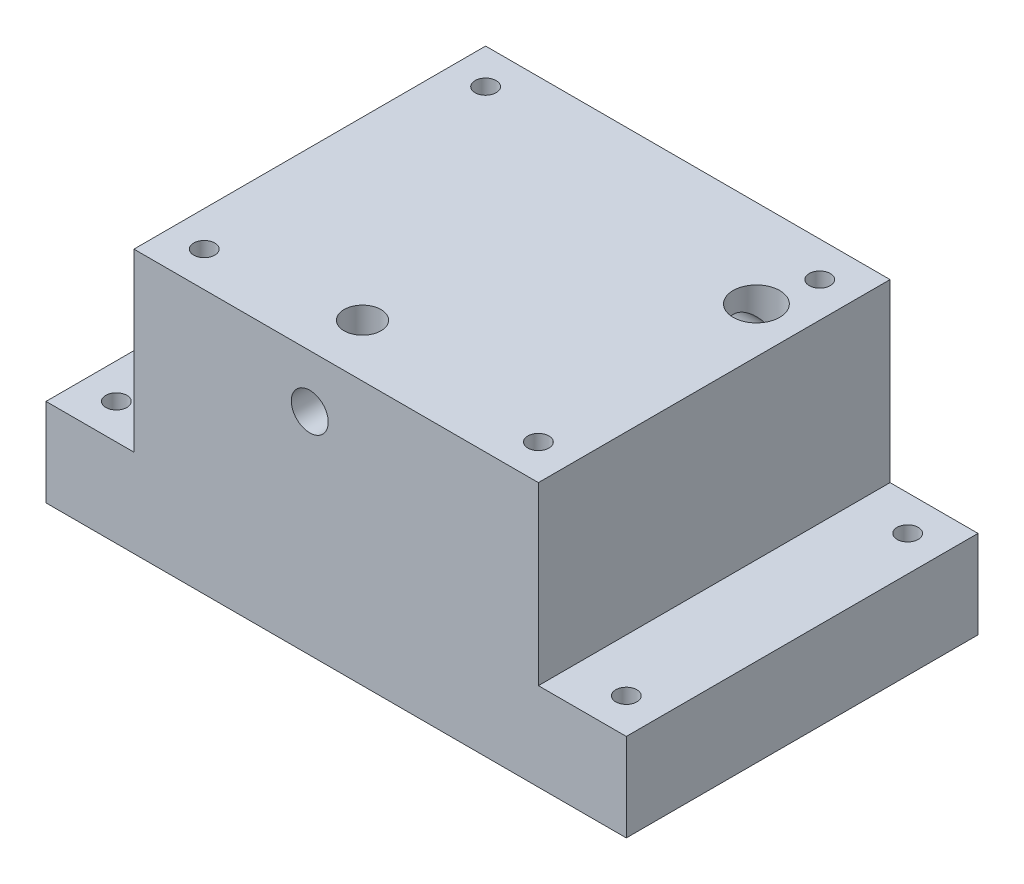
SolidWorks part; units mm, degrees
ref_plane "前视基准面" through (0, 0, 0) normal (0, 0, 1) x (1, 0, 0)
ref_plane "上视基准面" through (0, 0, 0) normal (0, 1, 0) x (1, 0, 0)
ref_plane "右视基准面" through (0, 0, 0) normal (1, 0, 0) x (0, 0, -1)
other "Configuration Table"
sketch "草图1" plane through (0, 0, 0) normal (0, 1, 0) x (1, 0, 0)
  line L1 (-165, 100) -> (165, 100)
  line L2 (-165, 100) -> (-165, -100)
  line L3 (-165, -100) -> (165, -100)
  line L4 (165, 100) -> (165, -100)
  line L5 (-165, 100) -> (165, -100) construction
  line L6 (-165, -100) -> (165, 100) construction
  point P0 (0, 0)
  dimension "D1" = 330
  dimension "D2" = 200
extrude "凸台-拉伸1" add sketch "草图1" along normal blind 50
sketch "草图2" plane through (0, 50, 0) normal (0, 1, 0) x (1, 0, 0)
  line L0 (-165, -100) -> (165, -100) construction
  line L1 (-115, 100) -> (115, 100)
  line L2 (-115, 100) -> (-115, -100)
  line L3 (-115, -100) -> (115, -100)
  line L4 (115, 100) -> (115, -100)
  line L5 (-115, 100) -> (115, -100) construction
  line L6 (-115, -100) -> (115, 100) construction
  point P0 (0, 0)
  dimension "D1" = 230
extrude "凸台-拉伸2" add sketch "草图2" along normal blind 100
sketch "草图4" plane through (0, 150, 0) normal (0, 1, 0) x (1, 0, 0)
  line L0 (-115, 100) -> (-115, -100) construction
  line L1 (115, -100) -> (115, 100) construction
  line L2 (115, 100) -> (-115, 100) construction
  line L3 (89, 50) -> (89, 100)
  point P0 (89, 50)
  point P1 (-15, -74.6655)
  dimension "D1" = 100
  dimension "D2" = 26
  dimension "D3" = 50
hole_wizard "M30 螺纹孔的螺纹孔钻头1" positions "草图10" profile "草图11" hole size "M30" standard "GB"
sketch "草图10" plane through (0, 150, 0) normal (0, 1, 0) x (1, 0, 0)
  point P0 (89, 50)
sketch "草图11" plane through (89, 150, -50) normal (1, 0, 0) x (0, 0, 1)
  line L0 (0, 0) -> (0, 40)
  line L1 (0, 40) -> (13.25, 32.0386)
  line L2 (13.25, 32.0386) -> (13.25, 0)
  line L5 (13.25, 0) -> (0, 0)
  line L10 (0, 40) -> (-13.25, 32.0386) construction
  line L11 (0, -6.35) -> (0, 107.95) construction
  dimension "孔直径" = 26.5
  dimension "孔深度" = 40
  dimension "导头角度" = 118
sketch "草图12" plane through (0, 0, 100) normal (0, 0, 1) x (1, 0, 0)
  line L0 (-115, 150) -> (115, 150) construction
  point P0 (-15, 120)
  dimension "D1" = 30
hole_wizard "M24 螺纹孔的螺纹孔钻头3" positions "草图17" profile "草图18" hole size "M24" standard "GB"
sketch "草图17" plane through (0, 0, 100) normal (0, 0, 1) x (1, 0, 0)
  point P0 (-15, 120)
sketch "草图18" plane through (-15, 120, 100) normal (1, 0, 0) x (0, -1, 0)
  line L0 (0, 0) -> (0, 150)
  line L1 (0, 150) -> (10.5, 143.691)
  line L2 (10.5, 143.691) -> (10.5, 0)
  line L5 (10.5, 0) -> (0, 0)
  line L10 (0, 150) -> (-10.5, 143.691) construction
  line L11 (0, -6.35) -> (0, 107.95) construction
  dimension "孔直径" = 21
  dimension "孔深度" = 150
  dimension "导头角度" = 118
ref_plane "基准面1" through (89, 0, 0) normal (1, 0, 0) x (0, 0, -1)
sketch "草图19" plane through (89, 0, 0) normal (1, 0, 0) x (0, 0, -1)
  line L0 (-100, 150) -> (100, 150) construction
  line L1 (100, 150) -> (100, 50) construction
  point P0 (50, 125)
  point P1 (0, 0)
  dimension "D1" = 25
  dimension "D2" = 50
hole_wizard "M30 螺纹孔的螺纹孔钻头2" positions "草图22" profile "草图23" hole size "M30" standard "GB"
sketch "草图22" plane through (89, 0, 0) normal (1, 0, 0) x (0, 0, -1)
  point P0 (50, 125)
sketch "草图23" plane through (89, 125, -50) normal (0, 1, 0) x (0, 0, -1)
  line L0 (0, 0) -> (0, 116)
  line L1 (0, 116) -> (13.25, 108.0386)
  line L2 (13.25, 108.0386) -> (13.25, 0)
  line L5 (13.25, 0) -> (0, 0)
  line L10 (0, 116) -> (-13.25, 108.0386) construction
  line L11 (0, -6.35) -> (0, 107.95) construction
  dimension "孔直径" = 26.5
  dimension "孔深度" = 116
  dimension "导头角度" = 118
sketch "草图24" plane through (0, 150, 0) normal (0, 1, 0) x (1, 0, 0)
  line L0 (-115, 100) -> (-115, -100) construction
  line L1 (115, 100) -> (-115, 100) construction
  line L2 (-115, 0) -> (-50.4683, 0)
  line L3 (0, 100) -> (0, 71.6696)
  point P0 (-95, 80)
  dimension "D1" = 20
  dimension "D2" = 20
hole_wizard "M14 螺纹孔的螺纹孔钻头3" positions "草图31" profile "草图32" hole size "M14" standard "GB"
sketch "草图31" plane through (0, 150, 0) normal (0, 1, 0) x (1, 0, 0)
  point P0 (-95, 80)
sketch "草图32" plane through (-95, 150, -80) normal (1, 0, 0) x (0, 0, 1)
  line L0 (0, 0) -> (0, 25)
  line L1 (0, 25) -> (6, 21.3948)
  line L2 (6, 21.3948) -> (6, 0)
  line L5 (6, 0) -> (0, 0)
  line L10 (0, 25) -> (-6, 21.3948) construction
  line L11 (0, -6.35) -> (0, 107.95) construction
  dimension "孔直径" = 12
  dimension "孔深度" = 25
  dimension "导头角度" = 118
ref_plane "基准面2" through (0, 0, 0) normal (0, 0, 1) x (1, 0, 0)
mirror "镜向1" about plane through (0, 0, 0) normal (0, 0, 1) of "M14 螺纹孔的螺纹孔钻头3"
ref_plane "基准面3" through (0, 0, 0) normal (-1, 0, 0) x (0, 0, 1)
mirror "镜向2" about plane through (0, 0, 0) normal (-1, 0, 0) of "镜向1", "M14 螺纹孔的螺纹孔钻头3"
sketch "草图33" plane through (0, 50, 0) normal (0, 1, 0) x (1, 0, 0)
  line L0 (-165, 100) -> (-165, -100) construction
  line L1 (-115, 100) -> (-165, 100) construction
  point P0 (-145, 80)
  dimension "D1" = 20
  dimension "D2" = 20
hole_wizard "M14 螺纹孔的螺纹孔钻头4" positions "草图34" profile "草图35" hole size "M14" standard "GB" end condition through all
sketch "草图34" plane through (0, 50, 0) normal (0, 1, 0) x (1, 0, 0)
  point P0 (-145, 80)
sketch "草图35" plane through (-145, 50, -80) normal (1, 0, 0) x (0, 0, 1)
  line L0 (0, 0) -> (0, 50)
  line L1 (0, 50) -> (6, 50)
  line L2 (6, 50) -> (6, 0)
  line L5 (6, 0) -> (0, 0)
  line L11 (0, -6.35) -> (0, 107.95) construction
  dimension "通孔孔直径" = 12
  dimension "通孔孔深度" = 50
sketch "草图36" plane through (0, 50, 0) normal (0, 1, 0) x (1, 0, 0)
  line L0 (-165, 100) -> (-165, -100) construction
  line L1 (-165, -100) -> (-115, -100) construction
  line L2 (165, 100) -> (115, 100) construction
  line L3 (165, -100) -> (165, 100) construction
  line L4 (115, -100) -> (165, -100) construction
  point P0 (-145, -80)
  point P1 (145, -80)
  point P2 (145, 80)
  point P7 (-144.4915, -94.7145)
  point P8 (-144.2611, -89.8751)
  point P15 (145, -87.3402)
  point P16 (145.8742, -91.2578)
  dimension "D1" = 20
  dimension "D2" = 20
  dimension "D3" = 20
  dimension "D4" = 20
  dimension "D5" = 20
  dimension "D6" = 20
sketch "草图41" plane through (0, 50, 0) normal (0, 1, 0) x (1, 0, 0)
  line L0 (-165, 0) -> (-115, 0)
  line L1 (-165, 100) -> (-165, -100) construction
  line L2 (-115, 100) -> (-115, -100) construction
  line L3 (0, 0) -> (0, -36.4109)
ref_plane "基准面4" through (0, 0, 0) normal (0, 0, 1) x (1, 0, 0)
mirror "镜向3" about plane through (0, 0, 0) normal (0, 0, 1) of "M14 螺纹孔的螺纹孔钻头4"
ref_plane "基准面5" through (0, 0, 0) normal (-1, 0, 0) x (0, 0, 1)
mirror "镜向5" about plane through (0, 0, 0) normal (-1, 0, 0) of "镜向3", "M14 螺纹孔的螺纹孔钻头4"
sketch "草图42" plane through (0, 150, 0) normal (0, 1, 0) x (1, 0, 0)
  line L0 (-115, 100) -> (-115, -100) construction
  line L1 (-115, -100) -> (115, -100) construction
  point P0 (-15, -70)
  dimension "D1" = 100
  dimension "D2" = 30
sketch "草图51" plane through (0, 150, 0) normal (0, 1, 0) x (1, 0, 0)
  line L0 (-115, -100) -> (115, -100) construction
  line L1 (-115, 100) -> (-115, -100) construction
  point P0 (-15, -70)
  dimension "D1" = 30
  dimension "D2" = 100
hole_wizard "M24 螺纹孔的螺纹孔钻头5" positions "草图55" profile "草图56" hole size "M24" standard "GB"
sketch "草图55" plane through (0, 150, 0) normal (0, 1, 0) x (1, 0, 0)
  line L0 (-115, -100) -> (115, -100) construction
  line L1 (-115, 100) -> (-115, -100) construction
  point P0 (-15, -70)
  dimension "D1" = 30
  dimension "D2" = 100
sketch "草图56" plane through (-15, 150, 70) normal (1, 0, 0) x (0, 0, 1)
  line L0 (0, 0) -> (0, 40)
  line L1 (0, 40) -> (10.5, 33.691)
  line L2 (10.5, 33.691) -> (10.5, 0)
  line L5 (10.5, 0) -> (0, 0)
  line L10 (0, 40) -> (-10.5, 33.691) construction
  line L11 (0, -6.35) -> (0, 107.95) construction
  dimension "孔直径" = 21
  dimension "孔深度" = 40
  dimension "导头角度" = 118
